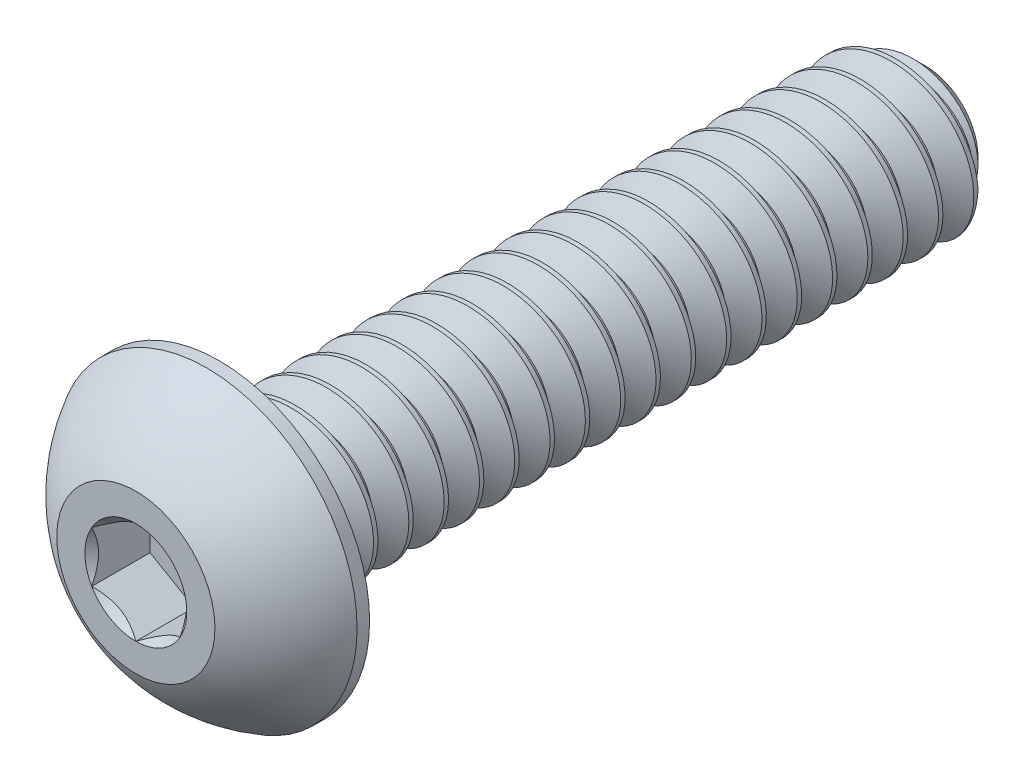
SolidWorks part; units mm, degrees
material "Plain Carbon Steel"
ref_plane "Front" through (0, 0, 0) normal (0, 0, 1) x (1, 0, 0)
ref_plane "Top" through (0, 0, 0) normal (0, 1, 0) x (1, 0, 0)
ref_plane "Right" through (0, 0, 0) normal (1, 0, 0) x (0, 0, -1)
sketch "Sketch1" plane through (0, 0, 0) normal (1, 0, 0) x (0, 0, -1)
  line L2 (1.4986, 1.4224) -> (14.1986, 1.4224)
  line L3 (14.1986, 1.4224) -> (14.1986, 0)
  line L4 (14.1986, 0) -> (1.4986, 0)
  line L6 (1.2738, 2.7051) -> (1.4986, 2.7051) construction
  line L7 (14.1986, 1.4224) -> (14.1986, -1.4224) construction
  line L8 (0, 0) -> (1.4986, 0) construction
  line L9 (1.4986, 2.7051) -> (1.4986, -2.7051) construction
  line L11 (1.4986, 1.4224) -> (1.4986, 0)
  line L13 (0, 0.7937) -> (0, -0.7937) construction
  line L14 (0, 0.7937) -> (0, 1.4224) construction
  arc A3 (0, 1.4224) -> (1.2738, 2.7051) centre (2.7151, 0) cw construction
  dimension "D1" = 0.2248
revolve "Revolve1" add sketch "Sketch1" angle 360 mid plane about L4
sketch "Sketch3" plane through (0, 0, -14.1986) normal (0, 0, -1) x (-1, 0, 0)
  circle A0 centre (0, 0) radius 1.4224
curve "Helix/Spiral1" pitch 0.635 height 13.335 radius 1.4224 centre (0, 0, -14.1986) axis (0, 0, 1) start towards (0, 1, 0)
sketch "Sketch2" plane through (0, 0, 0) normal (1, 0, 0) x (0, 0, -1)
  line L0 (14.1986, 1.4224) -> (14.7542, 1.4224)
  line L1 (14.7542, 1.4224) -> (14.5161, 1.01)
  line L2 (14.5161, 1.01) -> (14.4367, 1.01)
  line L3 (14.4367, 1.01) -> (14.1986, 1.4224)
  line L4 (14.3177, 1.2162) -> (14.6352, 1.2162) construction
  dimension "D1" = 60
  dimension "D2" = 0.0794
  dimension "D3" = 0.3175
chamfer "Chamfer1" distance 0.4763 angle 45 1 edges at (0, 1.4224, -14.1986)
sweep "Cut-Sweep1" cut profiles "Sketch2" path "Helix/Spiral1" align with end faces yes
sketch "Sketch7" plane through (0, 0, 0) normal (1, 0, 0) x (0, 0, -1)
  line L6 (1.2738, 2.7051) -> (1.4986, 2.7051) construction
  line L8 (0, 0) -> (1.4986, 0) construction
  line L11 (1.4986, 2.7051) -> (1.4986, -2.7051) construction
  line L12 (1.2738, 2.7051) -> (1.4986, 2.7051)
  line L13 (0, 0) -> (1.4986, 0)
  line L14 (0, 0.7937) -> (0, -0.7937) construction
  line L15 (1.4986, 2.7051) -> (1.4986, 0)
  line L16 (0, 1.4224) -> (0, 0)
  arc A2 (1.2738, 2.7051) -> (0, 1.4224) centre (2.7151, 0) ccw construction
  arc A3 (1.2738, 2.7051) -> (0, 1.4224) centre (2.7151, 0) ccw
revolve "Revolve2" add sketch "Sketch7" angle 360 mid plane about L13
sketch "Sketch5" plane through (0, 0, 0) normal (0, 0, 1) x (1, 0, 0)
  line L1 (0.7937, -0.4583) -> (0.7937, 0.4583)
  line L2 (0.7937, 0.4583) -> (0, 0.9165)
  line L3 (0, 0.9165) -> (-0.7937, 0.4583)
  line L4 (-0.7937, 0.4583) -> (-0.7937, -0.4583)
  line L5 (-0.7937, -0.4583) -> (0, -0.9165)
  line L6 (0, -0.9165) -> (0.7937, -0.4583)
  circle A0 centre (0, 0) radius 0.7937 construction
extrude "Cut-Extrude2" cut sketch "Sketch5" against normal blind 1.049
sketch "Sketch6" plane through (0, 0, 0) normal (0, 0, 1) x (1, 0, 0)
  circle A0 centre (0, 0) radius 0.9165
extrude "Cut-Extrude3" cut sketch "Sketch6" against normal blind 1.049 draft 45
sketch "Sketch9" [suppressed] plane through (0, 0, -1.4986) normal (0, 0, 1) x (1, 0, 0)
  circle A2 centre (0, 0) radius 1.4224
extrude "Boss-Extrude2" [suppressed] add sketch "Sketch9" against normal offset from surface (6.35 mm away) 28.575 up to face at (0, 0.9462, -14.1986)
sketch "Sketch10" plane through (0, 0, 0) normal (1, 0, 0) x (0, 0, -1)
  line L0 (14.1986, 1.4224) -> (14.1986, -1.4224) construction
  point P0 (13.2461, -1.4224)
  dimension "D1" = 0.9525
equation "\"D3@Helix/Spiral1\" = \"Lg@Sketch1\" + \"D4@Helix/Spiral1\""
equation "\"D2@Sketch2\" = \"D4@Helix/Spiral1\" * .125"
equation "\"D3@Sketch2\" = \"D4@Helix/Spiral1\" * .5"
equation "\"D1@Chamfer1\" = \"D4@Helix/Spiral1\" * .75"
equation "\"D1@Cut-Extrude2\" = \"Head Ht@Sketch1\" * .7"
equation "\"D1@Sketch1\" = \"Head Ht@Sketch1\" * .15"
equation "\"D1@Sketch10\" = \"D4@Helix/Spiral1\" * 1.5"
equation "\"D1@Cut-Extrude3\" = \"D1@Cut-Extrude2\""
